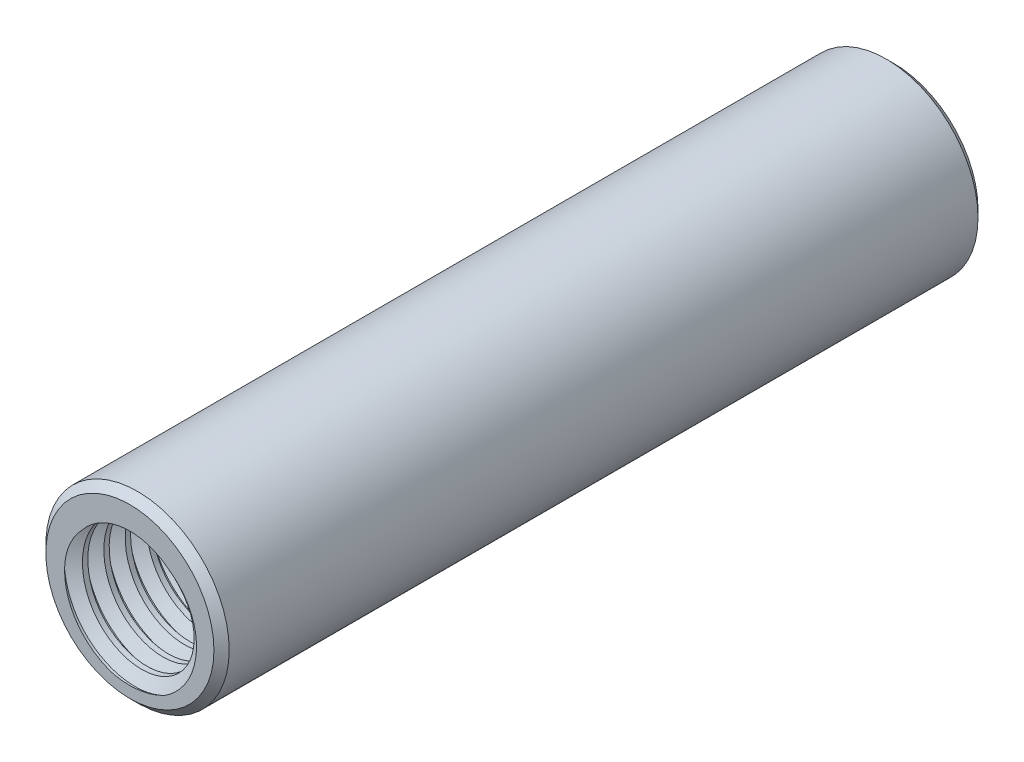
SolidWorks part; units mm, degrees
ref_plane "Front Plane" through (0, 0, 0) normal (0, 0, 1) x (1, 0, 0)
ref_plane "Top Plane" through (0, 0, 0) normal (0, 1, 0) x (1, 0, 0)
ref_plane "Right Plane" through (0, 0, 0) normal (1, 0, 0) x (0, 0, -1)
sketch "Sketch1" plane through (0, 0, 0) normal (0, 0, 1) x (1, 0, 0)
  circle A0 centre (0, 0) radius 3
  circle A1 centre (0, 0) radius 2
  dimension "D1" = 6
  dimension "D2" = 4
extrude "Boss-Extrude1" add sketch "Sketch1" along normal blind 25
thread "Thread1" pitch 0.7 profile "Thread Profile1" start angle 0, offset 1, length 0, pitch 0.7, diameter 4
ref_plane "Plane1" through (2, 0, -1) normal (0, -1, 0) x (1, 0, 0)
sketch "Thread Profile1" plane through (2, 0, -1) normal (0, -1, 0) x (1, 0, 0)
  line L0 (0, 0) -> (0, 0.7) construction
  line L1 (0, 0) -> (0.3789, 0.2187)
  line L2 (0.3789, 0.2187) -> (0.3789, 0.3062)
  line L3 (0.3789, 0.3062) -> (0, 0.525)
  line L4 (0.3789, 0.2625) -> (0, 0.2625) construction
  line L11 (0, 0) -> (0, 0.525)
  point P2 (0, 0)
  dimension "Pitch" = 0.7
  dimension "Profile_Angle" = 60
  dimension "Profile_Land" = 0.0875
  dimension "Profile_Height" = 0.3789
chamfer "Chamfer1" distance 0.25 angle 45 2 edges at (3, 0, 0) (3, 0, 25)
